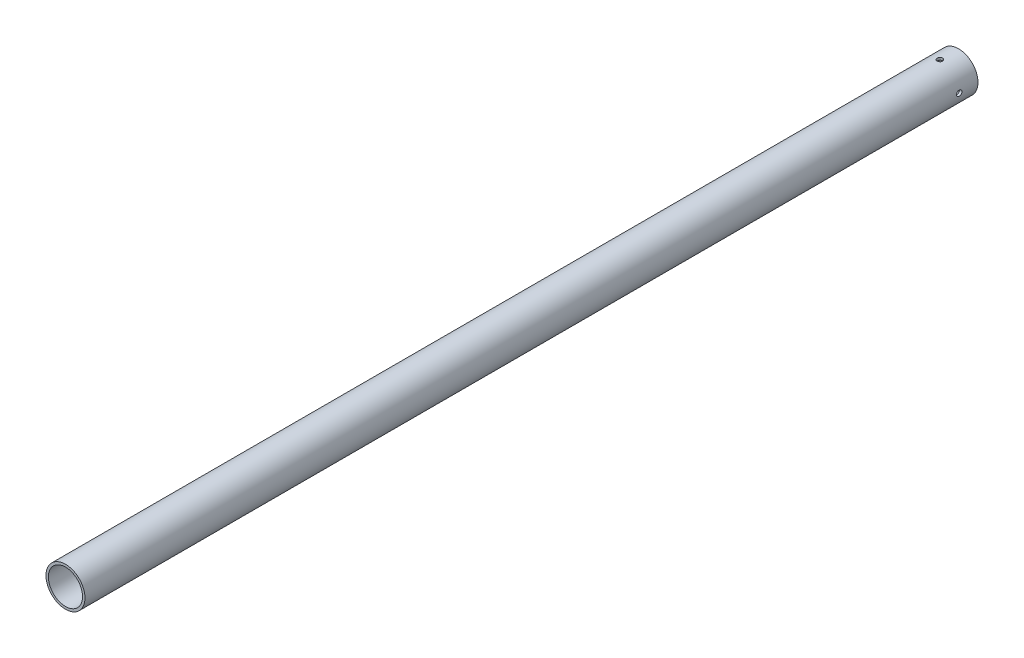
SolidWorks part; units mm, degrees
material "PC High Viscosity"
ref_plane "Front Plane" through (0, 0, 0) normal (0, 0, 1) x (1, 0, 0)
ref_plane "Top Plane" through (0, 0, 0) normal (0, 1, 0) x (1, 0, 0)
ref_plane "Right Plane" through (0, 0, 0) normal (1, 0, 0) x (0, 0, -1)
sketch "Sketch2" plane through (0, 0, 0) normal (0, 0, 1) x (1, 0, 0)
  circle A0 centre (0, 0) radius 11.1125
  circle A1 centre (0, 0) radius 12.7
  dimension "D1" = 25.4
  dimension "D2" = 1.5875
extrude "Boss-Extrude1" add sketch "Sketch2" along normal mid plane 581.2193
sketch "Sketch3" plane through (0, 0, 0) normal (0, 1, 0) x (1, 0, 0)
  line L0 (12.7, 290.6096) -> (-12.7, 290.6096) construction
  circle A0 centre (0, 278.4176) radius 1.7526
  dimension "D1" = 3.5052
  dimension "D2" = 12.192
extrude "Cut-Extrude1" cut sketch "Sketch3" against normal through all both and the other way through all
sketch "Sketch5" plane through (0, 0, 0) normal (1, 0, 0) x (0, 0, -1)
  line L0 (290.6096, -12.7) -> (290.6096, 12.7) construction
  circle A0 centre (278.4176, 0) radius 1.7526
  dimension "D1" = 3.5052
  dimension "D2" = 12.192
extrude "Cut-Extrude2" cut sketch "Sketch5" against normal through all both and the other way through all
